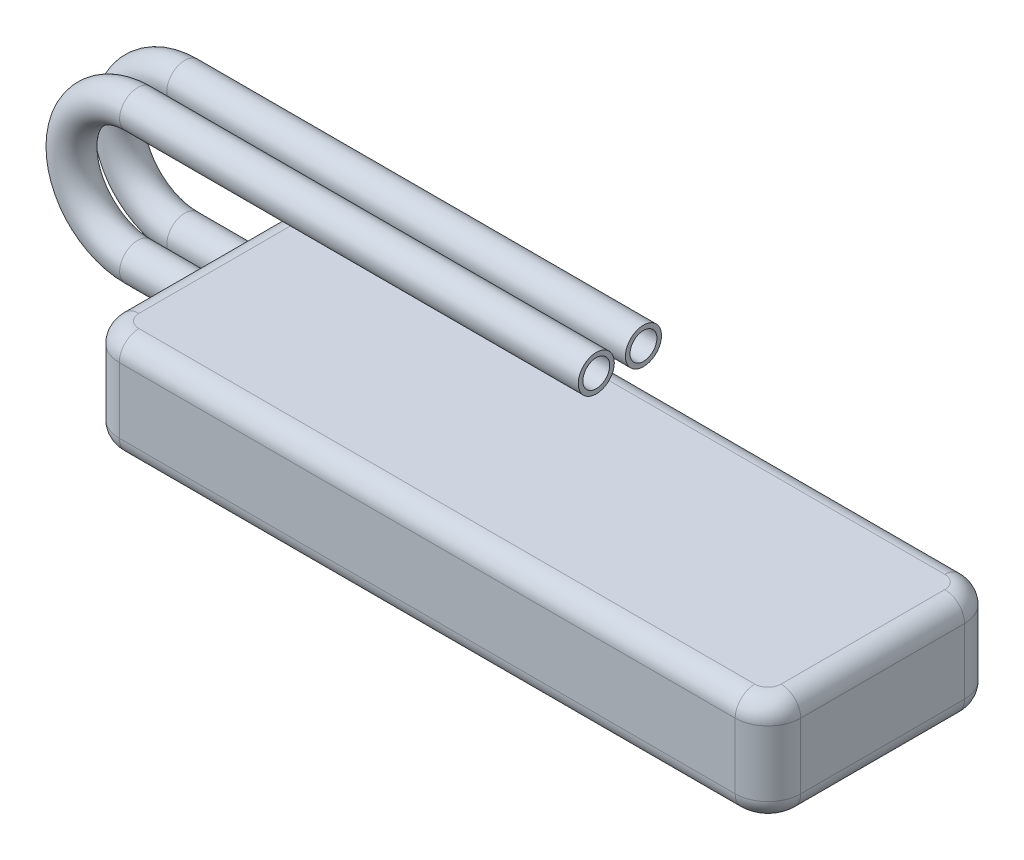
SolidWorks part; units mm, degrees
ref_plane "前视基准面" through (0, 0, 0) normal (0, 0, 1) x (1, 0, 0)
ref_plane "上视基准面" through (0, 0, 0) normal (0, 1, 0) x (1, 0, 0)
ref_plane "右视基准面" through (0, 0, 0) normal (1, 0, 0) x (0, 0, -1)
other "Configuration Table"
sketch "草图1" plane through (0, 0, 0) normal (0, 0, 1) x (1, 0, 0)
  line L1 (0, 0) -> (104, 0)
  line L2 (0, 0) -> (0, 16)
  line L3 (0, 16) -> (104, 16)
  line L4 (104, 0) -> (104, 16)
  dimension "D1" = 104
  dimension "D2" = 16
extrude "凸台-拉伸1" add sketch "草图1" against normal blind 35
sketch "草图2" plane through (0, 0, 0) normal (1, 0, 0) x (0, 0, -1)
  line L0 (35, 16) -> (0, 16) construction
  line L1 (35, 16) -> (35, 0) construction
  line L2 (35, 16) -> (0, 16) construction
  circle A0 centre (25, 10) radius 2.05
  circle A1 centre (25, 10) radius 2.75
  circle A2 centre (17.8, 10) radius 2.05
  circle A3 centre (17.8, 10) radius 2.75
  dimension "D1" = 4.1
  dimension "D2" = 5.5
  dimension "D3" = 4.1
  dimension "D4" = 5.5
  dimension "D6" = 6
  dimension "D7" = 10
  dimension "D5" = 7.2
  dimension "D8" = 6
sketch "草图3" plane through (0, 0, 0) normal (0, 0, 1) x (1, 0, 0)
  line L0 (0, 11.6) -> (-10, 11.6)
  line L1 (0, 9.55) -> (0, 13.65) construction
  line L2 (-10, 28.6) -> (60, 28.6)
  arc A0 (-10, 11.6) -> (-10, 28.6) centre (-10, 20.1) cw
  dimension "D1" = 70
sweep "扫描1" add profiles "草图2" path "草图3"
fillet "圆角1" radius 3 8 edges at (104, 0, -17.5) (52, 0, -35) (0, 0, -17.5) (52, 0, 0) (0, 16, -17.5) (52, 16, -35) (104, 16, -17.5) (52, 16, 0)
fillet "圆角2" radius 5 12 edges at (0.8787, 0.8787, -0.8787) (0.8787, 15.1213, -0.8787) (103.1213, 15.1213, -0.8787) (103.1213, 0.8787, -0.8787) (103.1213, 15.1213, -34.1213) (103.1213, 0.8787, -34.1213) (0.8787, 0.8787, -34.1213) (0.8787, 15.1213, -34.1213) (0, 8, -35) (104, 8, -35) (104, 8, 0) (0, 8, 0)
